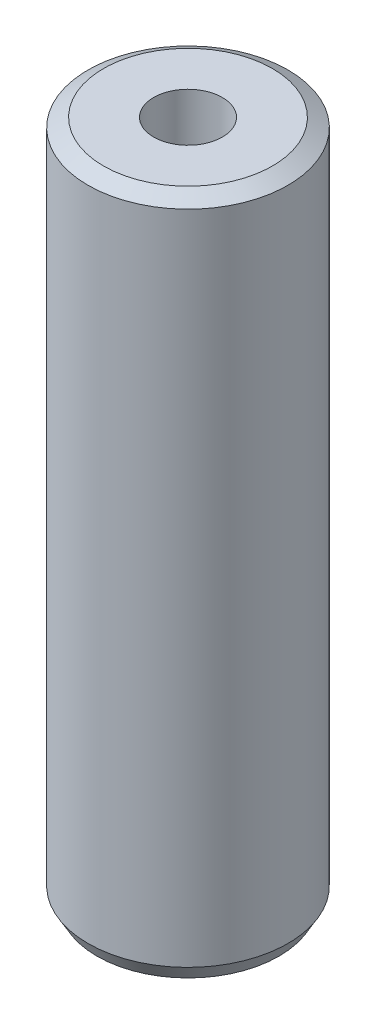
SolidWorks part; units mm, degrees
ref_plane "Front Plane" through (0, 0, 0) normal (0, 0, 1) x (1, 0, 0)
ref_plane "Top Plane" through (0, 0, 0) normal (0, 1, 0) x (1, 0, 0)
ref_plane "Right Plane" through (0, 0, 0) normal (1, 0, 0) x (0, 0, -1)
sketch "Sketch1" plane through (0, 0, 0) normal (0, 1, 0) x (1, 0, 0)
  circle A0 centre (0, 0) radius 30
  dimension "SHAFT_OD" = 60
extrude "Boss-Extrude1" add sketch "Sketch1" along normal blind 204.3906
sketch "Sketch2" plane through (0, 0, 0) normal (0, 1, 0) x (1, 0, 0)
  circle A0 centre (0, 0) radius 10.3048
  dimension "BORE_D" = 20.6096
extrude "Cut-Extrude1" cut sketch "Sketch2" along normal through all
chamfer "Chamfer1" distance 2.6846 angle 60 2 edges at (0, 204.3906, 30) (0, 0, 30) first distance on face at (0, 204.3906, 30) first distance on face at (0, 0, 10.3048)
